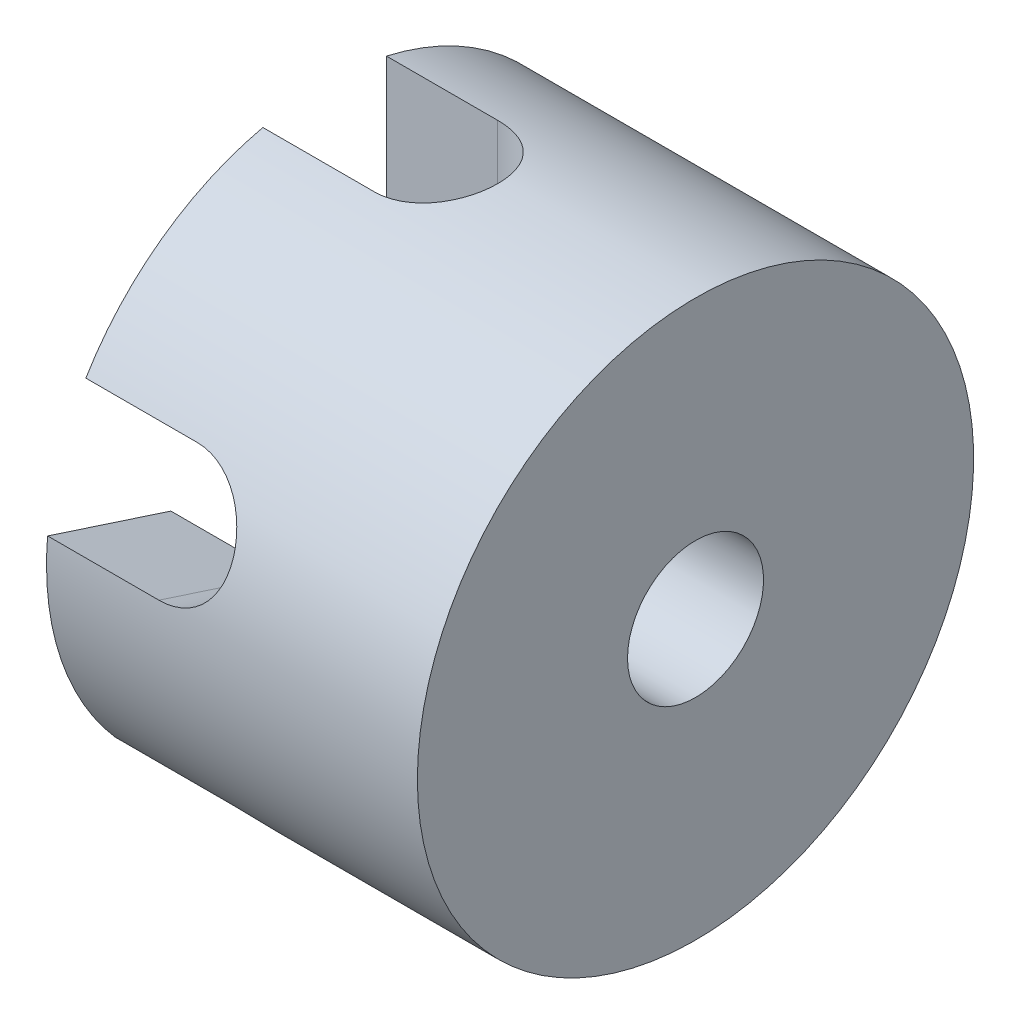
SolidWorks part; units mm, degrees
ref_plane "Front Plane" through (0, 0, 0) normal (0, 0, 1) x (1, 0, 0)
ref_plane "Top Plane" through (0, 0, 0) normal (0, 1, 0) x (1, 0, 0)
ref_plane "Right Plane" through (0, 0, 0) normal (1, 0, 0) x (0, 0, -1)
sketch "Sketch1" plane through (0, 0, 0) normal (0, 0, 1) x (1, 0, 0)
  line L0 (0, 0) -> (32462.4085, 0) construction
  line L1 (-12.5153, 22.5) -> (17.4847, 22.5)
  line L2 (17.4847, 22.5) -> (17.4847, 5.5)
  line L3 (17.4847, 5.5) -> (7.4847, 5.5)
  line L4 (7.4847, 5.5) -> (7.4847, 12.5)
  line L5 (7.4847, 12.5) -> (-12.5153, 12.5)
  line L6 (-12.5153, 22.5) -> (-12.5153, 12.5)
  dimension "D1" = 30
  dimension "D2" = 20
  dimension "D3" = 10
  dimension "D4" = 11
  dimension "D5" = 45
revolve "Revolve1" add sketch "Sketch1" angle 360 about L0
ref_plane "Plane1" through (-12.5153, 0, 0) normal (-1, 0, 0) x (0, 0, 1)
sketch "Sketch2" plane through (-12.5153, 0, 0) normal (-1, 0, 0) x (0, 0, 1)
  line L5 (0, 7.9125) -> (5, 7.9125)
  line L10 (5, 7.9125) -> (5, 31.4531)
  line L11 (5, 31.4531) -> (-5, 31.4531)
  line L12 (-5, 31.4531) -> (-5, 7.9125)
  line L13 (0, 7.9125) -> (-5, 7.9125)
  point P0 (0, 0)
extrude "Cut-Extrude1" cut sketch "Sketch2" against normal blind 14
fillet "Fillet1" radius 5 2 edges at (1.4847, 16.6969, -5) (1.4847, 16.6969, 5)
pattern_circular "CirPattern1" count 5 over 360 about axis through (0, 0, 0) along (1, 0, 0) of "Cut-Extrude1", "Fillet1"
